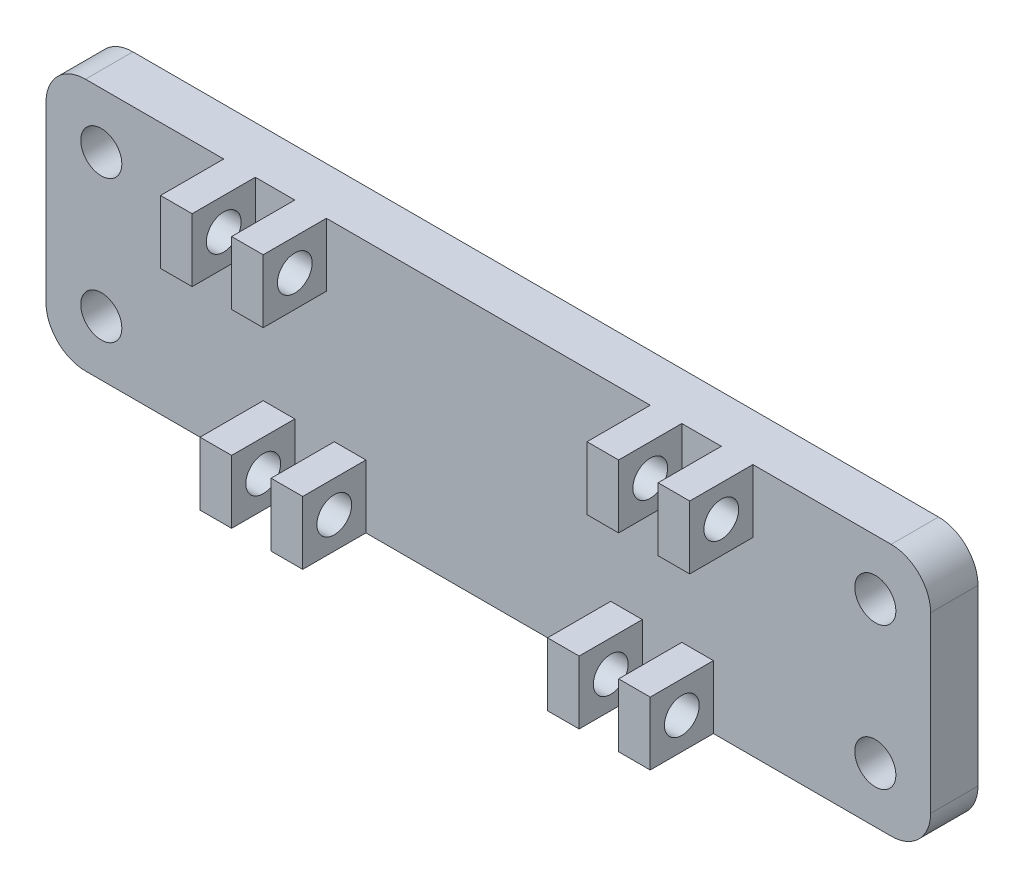
SolidWorks part; units mm, degrees
ref_plane "前视基准面" through (0, 0, 0) normal (0, 0, 1) x (1, 0, 0)
ref_plane "上视基准面" through (0, 0, 0) normal (0, 1, 0) x (1, 0, 0)
ref_plane "右视基准面" through (0, 0, 0) normal (1, 0, 0) x (0, 0, -1)
sketch "草图2" plane through (0, 0, 0) normal (0, 0, 1) x (1, 0, 0)
  line L0 (52.5, -4.5) -> (-3.5, -4.5) construction
  line L1 (-1, -12.5) -> (50, -12.5)
  line L2 (-3.5, -10) -> (-3.5, 1)
  line L3 (-1, 3.5) -> (50, 3.5)
  line L4 (-1, -81.5) -> (50, -81.5)
  line L5 (52.5, -79) -> (52.5, 1)
  line L6 (50, 3.5) -> (-1, 3.5)
  line L7 (-3.5, 1) -> (-3.5, -79)
  line L8 (-1, -81.5) -> (50, -81.5)
  line L9 (52.5, -10) -> (52.5, 1)
  line L10 (50, 3.5) -> (-1, 3.5)
  line L11 (-3.5, 1) -> (-3.5, -79)
  line L12 (52.5, -12.5) -> (52.5, 1)
  circle A0 centre (49, 0) radius 1.3
  circle A1 centre (0, 0) radius 1.3
  arc A2 (-1, 3.5) -> (-3.5, 1) centre (-1, 1) ccw
  arc A3 (52.5, 1) -> (50, 3.5) centre (50, 1) ccw
  arc A4 (-3.5, -79) -> (-1, -81.5) centre (-1, -79) ccw
  arc A5 (50, -81.5) -> (52.5, -79) centre (50, -79) ccw
  arc A6 (52.5, 1) -> (50, 3.5) centre (50, 1) ccw
  arc A7 (-1, 3.5) -> (-3.5, 1) centre (-1, 1) ccw
  arc A8 (-3.5, -79) -> (-1, -81.5) centre (-1, -79) ccw
  arc A9 (50, -81.5) -> (52.5, -79) centre (50, -79) ccw
  arc A10 (52.5, 1) -> (50, 3.5) centre (50, 1) ccw
  arc A11 (-1, 3.5) -> (-3.5, 1) centre (-1, 1) ccw
  arc A12 (50, -12.5) -> (52.5, -10) centre (50, -10) ccw
  arc A13 (-3.5, -10) -> (-1, -12.5) centre (-1, -10) ccw
  circle A14 centre (0, -9) radius 1.3
  circle A15 centre (49, -9) radius 1.3
  point P31 (-3.5, -12.5)
  line M16 (52.5, -79) -> (52.5, 1)
  arc M17 (52.5, 1) -> (50, 3.5) centre (50, 1) ccw
  line M18 (50, 3.5) -> (-1, 3.5)
  arc M19 (-1, 3.5) -> (-3.5, 1) centre (-1, 1) ccw
  line M20 (-3.5, 1) -> (-3.5, -79)
  circle M21 centre (49, 0) radius 1.3
  circle M22 centre (0, 0) radius 1.3
  dimension "D4" = 2.6
  dimension "D5" = 2.6
  dimension "D6" = 2.5
  dimension "D7" = 2.5
  dimension "D8" = 2.5
  dimension "D9" = 2.5
  dimension "D2" = 16
  dimension "D3" = 0
  dimension "D1" = 0
extrude "凸台-拉伸2" add sketch "草图2" along normal blind 3 contours L1 M20 M16 M17 M18 M19 M22 M21 | L0 L11 A13 L1 A12 A15 A14 M16 region at (24.5, -8.4665, 0) region at (24.5, -0.5335, 0)
sketch "草图4" plane through (0, 0, 3) normal (0, 0, 1) x (1, 0, 0)
  line L0 (24.5, 3.5) -> (24.5, -12.5) construction
  line L1 (7.75, 1.5) -> (14.25, 1.5) construction
  line L4 (-3.5, 1) -> (-3.5, -10)
  line L5 (-1, -12.5) -> (50, -12.5)
  line L6 (52.5, -10) -> (52.5, 1)
  line L7 (50, 3.5) -> (-1, 3.5)
  line L8 (-3.5, 1) -> (-3.5, -10)
  line L10 (52.5, -10) -> (52.5, 1)
  line L11 (50, 3.5) -> (-1, 3.5)
  line L14 (7.75, 3.5) -> (14.25, 3.5)
  line L15 (7.75, 3.5) -> (7.75, -0.5)
  line L16 (7.75, -0.5) -> (14.25, -0.5)
  line L17 (14.25, 3.5) -> (14.25, -0.5)
  line L18 (39.25, -0.5) -> (36.75, 3.5) construction
  line L19 (9.75, 3.5) -> (12.25, 3.5)
  line L20 (9.75, 3.5) -> (9.75, -0.5)
  line L21 (9.75, -0.5) -> (12.25, -0.5)
  line L22 (12.25, 3.5) -> (12.25, -0.5)
  line L23 (9.75, 3.5) -> (12.25, -0.5) construction
  line L24 (9.75, -0.5) -> (12.25, 3.5) construction
  line L25 (39.25, 3.5) -> (36.75, -0.5) construction
  line L26 (41.25, 1.5) -> (34.75, 1.5) construction
  line L27 (36.75, 3.5) -> (36.75, -0.5)
  line L28 (39.25, -0.5) -> (36.75, -0.5)
  line L29 (39.25, 3.5) -> (39.25, -0.5)
  line L30 (39.25, 3.5) -> (36.75, 3.5)
  line L31 (34.75, 3.5) -> (34.75, -0.5)
  line L32 (41.25, -0.5) -> (34.75, -0.5)
  line L33 (41.25, 3.5) -> (41.25, -0.5)
  line L34 (41.25, 3.5) -> (34.75, 3.5)
  line L35 (10.25, -10.5) -> (16.75, -10.5) construction
  line L36 (10.25, -12.5) -> (16.75, -12.5)
  line L37 (10.25, -12.5) -> (10.25, -8.5)
  line L38 (10.25, -8.5) -> (16.75, -8.5)
  line L39 (16.75, -12.5) -> (16.75, -8.5)
  line L40 (36.75, -8.5) -> (34.25, -12.5) construction
  line L41 (12.25, -12.5) -> (14.75, -12.5)
  line L42 (12.25, -12.5) -> (12.25, -8.5)
  line L43 (12.25, -8.5) -> (14.75, -8.5)
  line L44 (14.75, -12.5) -> (14.75, -8.5)
  line L45 (12.25, -12.5) -> (14.75, -8.5) construction
  line L46 (12.25, -8.5) -> (14.75, -12.5) construction
  line L47 (36.75, -12.5) -> (34.25, -8.5) construction
  line L48 (38.75, -10.5) -> (32.25, -10.5) construction
  line L49 (34.25, -12.5) -> (34.25, -8.5)
  line L50 (36.75, -8.5) -> (34.25, -8.5)
  line L51 (36.75, -12.5) -> (36.75, -8.5)
  line L52 (36.75, -12.5) -> (34.25, -12.5)
  line L53 (32.25, -12.5) -> (32.25, -8.5)
  line L54 (38.75, -8.5) -> (32.25, -8.5)
  line L55 (38.75, -12.5) -> (38.75, -8.5)
  line L56 (38.75, -12.5) -> (32.25, -12.5)
  line L62 (-1, -12.5) -> (50, -12.5)
  arc A2 (52.5, 1) -> (50, 3.5) centre (50, 1) ccw
  arc A3 (-1, 3.5) -> (-3.5, 1) centre (-1, 1) ccw
  arc A4 (52.5, 1) -> (50, 3.5) centre (50, 1) ccw
  arc A5 (-1, 3.5) -> (-3.5, 1) centre (-1, 1) ccw
  arc A8 (-3.5, -10) -> (-1, -12.5) centre (-1, -10) ccw
  arc A10 (-3.5, -10) -> (-1, -12.5) centre (-1, -10) ccw
  arc A12 (50, -12.5) -> (52.5, -10) centre (50, -10) ccw
  arc A13 (50, -12.5) -> (52.5, -10) centre (50, -10) ccw
  point P16 (11, 1.5)
  point P31 (38, 1.5)
  point P38 (13.5, -10.5)
  point P53 (35.5, -10.5)
  line M10 (-1, -12.5) -> (50, -12.5)
  dimension "D2" = 4
  dimension "D3" = 6.5
  dimension "D4" = 2.5
  dimension "D5" = 27
  dimension "D6" = 2.5
  dimension "D7" = 6.5
  dimension "D8" = 0
  dimension "D1" = 0
extrude "凸台-拉伸3" add sketch "草图4" along normal blind 4 contours L20 L11 L15 L16 | L11 L22 L16 L17 | L32 L27 L11 L31 | L33 L11 L29 L32 | L62 L42 L38 L37 | L44 L62 L39 L38 | L49 L54 L53 L62 | L55 L54 L51 M10 region at (8.75, 1.5, 3) region at (11.25, -10.5, 3) region at (13.25, 1.5, 3) region at (15.75, -10.5, 3) region at (35.75, 1.5, 3) region at (33.25, -10.5, 3) region at (40.25, 1.5, 3) region at (37.75, -10.5, 3)
sketch "草图6" plane through (7.75, 0, 0) normal (-1, 0, 0) x (0, 0, 1)
  line L0 (7, 3.5) -> (3, -0.5) construction
  line L1 (7, -8.5) -> (3, -12.5) construction
  line L4 (3, 3.5) -> (3, -0.5)
  line L5 (3, -0.5) -> (7, -0.5)
  line L6 (7, -0.5) -> (7, 3.5)
  line L7 (7, 3.5) -> (3, 3.5)
  line L8 (3, 3.5) -> (3, -0.5)
  line L9 (3, -0.5) -> (7, -0.5)
  line L10 (7, -0.5) -> (7, 3.5)
  line L11 (7, 3.5) -> (3, 3.5)
  line L12 (3, -8.5) -> (3, -12.5)
  line L13 (3, -12.5) -> (7, -12.5)
  line L14 (7, -12.5) -> (7, -8.5)
  line L15 (7, -8.5) -> (3, -8.5)
  line L16 (3, -8.5) -> (3, -12.5)
  line L17 (3, -12.5) -> (7, -12.5)
  line L18 (7, -12.5) -> (7, -8.5)
  line L19 (7, -8.5) -> (3, -8.5)
  circle A0 centre (5, 1.5) radius 1.1
  circle A1 centre (5, -10.5) radius 1.1
  dimension "D3" = 2.2
  dimension "D4" = 2.2
  dimension "D1" = 0
  dimension "D2" = 0
extrude "切除-拉伸2" cut sketch "草图6" against normal through all contours A0 | A1 region at (7.75, 1.5, 5) region at (7.75, -10.5, 5)
